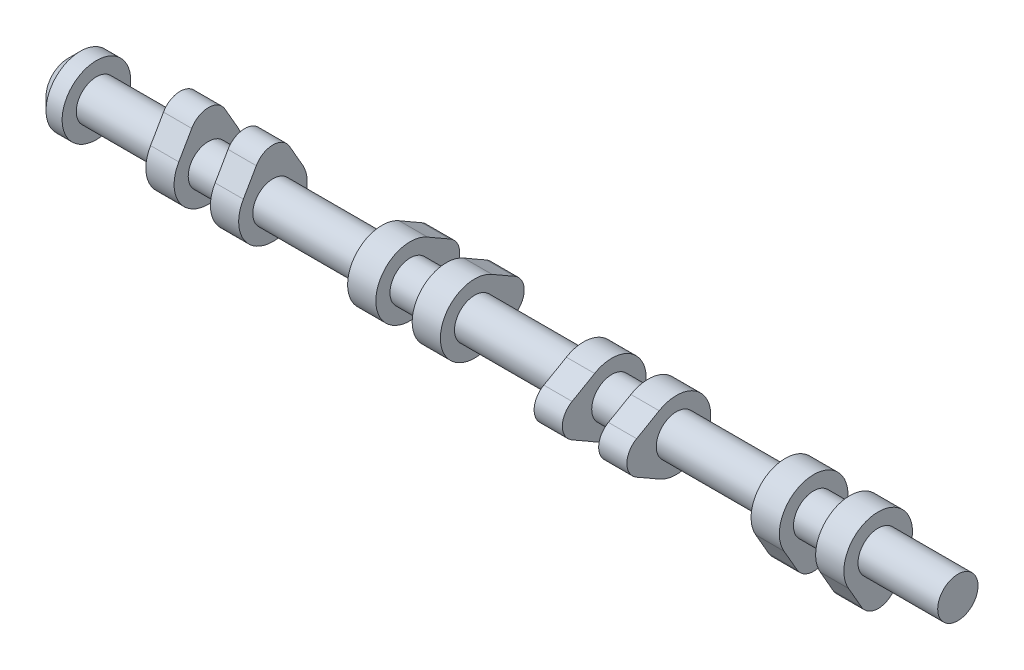
SolidWorks part; units mm, degrees
note: The reader was unsure of these and kept them because the rebuilt part matched: shared geometry of "Sketch1<5>", "Sketch1<6>".
ref_plane "Front Plane" through (0, 0, 0) normal (0, 0, 1) x (1, 0, 0)
ref_plane "Top Plane" through (0, 0, 0) normal (0, 1, 0) x (1, 0, 0)
ref_plane "Right Plane" through (0, 0, 0) normal (1, 0, 0) x (0, 0, -1)
sketch "Sketch1" plane through (0, 0, 0) normal (0, 0, 1) x (1, 0, 0)
  line L0 (0, 0) -> (10, 0)
  line L1 (10, 0) -> (46.5, 0)
  line L2 (46.5, 0) -> (78.5, 0)
  line L3 (78.5, 0) -> (146.5, 0)
  line L4 (146.5, 0) -> (178.5, 0)
  line L5 (178.5, 0) -> (246.5, 0)
  line L6 (246.5, 0) -> (278.5, 0)
  line L7 (278.5, 0) -> (346.5, 0)
  line L8 (346.5, 0) -> (378.5, 0)
  line L9 (378.5, 0) -> (415, 0)
  line L10 (415, 0) -> (425, 0)
  line L11 (39.5, 0) -> (53.5, 0) construction
  line L12 (71.5, 0) -> (85.5, 0) construction
  line L13 (139.5, 0) -> (153.5, 0) construction
  line L14 (185.5, 0) -> (171.5, 0) construction
  line L15 (239.5, 0) -> (253.5, 0)
  line L16 (271.5, 0) -> (285.5, 0)
  line L17 (339.5, 0) -> (353.5, 0)
  line L18 (371.5, 0) -> (385.5, 0)
  line L19 (139.5, 0) -> (139.5, 7)
  line L20 (0, 0) -> (425, 0)
  line L21 (0, 0) -> (0, -10)
  line L22 (0, -10) -> (425, -10)
  line L23 (425, 0) -> (425, -10)
  line L24 (39.5, 0) -> (53.5, 0)
  line L25 (39.5, 0) -> (39.5, 7)
  line L26 (39.5, 7) -> (53.5, 7)
  line L27 (53.5, 0) -> (53.5, 7)
  line L28 (85.5, 0) -> (71.5, 0)
  line L29 (85.5, 0) -> (85.5, 7)
  line L30 (85.5, 7) -> (71.5, 7)
  line L31 (71.5, 0) -> (71.5, 7)
  line L32 (139.5, 0) -> (153.5, 0)
  line L33 (153.5, 0) -> (153.5, 7)
  line L34 (139.5, 7) -> (153.5, 7)
  line L35 (185.5, 0) -> (185.5, 7)
  line L36 (185.5, 0) -> (171.5, 0)
  line L37 (171.5, 0) -> (171.5, 7)
  line L38 (185.5, 7) -> (171.5, 7)
  line L39 (239.5, 0) -> (239.5, 7)
  line L40 (239.5, 0) -> (253.5, 0)
  line L41 (253.5, 0) -> (253.5, 7)
  line L42 (239.5, 7) -> (253.5, 7)
  line L43 (285.5, 0) -> (285.5, 7)
  line L44 (285.5, 0) -> (271.5, 0)
  line L45 (271.5, 0) -> (271.5, 7)
  line L46 (285.5, 7) -> (271.5, 7)
  line L47 (339.5, 0) -> (339.5, 7)
  line L48 (339.5, 0) -> (353.5, 0)
  line L49 (353.5, 0) -> (353.5, 7)
  line L50 (339.5, 7) -> (353.5, 7)
  line L51 (385.5, 0) -> (385.5, 7)
  line L52 (385.5, 0) -> (371.5, 0)
  line L53 (371.5, 0) -> (371.5, 7)
  line L54 (385.5, 7) -> (371.5, 7)
  line L55 (53.5, 0) -> (54.5, 0)
  line L56 (54.5, 0) -> (70.5, 0)
  line L57 (70.5, 0) -> (71.5, 0)
  line L58 (154.5, 0) -> (154.5, 7)
  line L59 (54.5, 0) -> (70.5, 0)
  line L60 (54.5, 0) -> (54.5, 7)
  line L61 (54.5, 7) -> (70.5, 7)
  line L62 (70.5, 0) -> (70.5, 7)
  line L63 (154.5, 0) -> (170.5, 0)
  line L64 (170.5, 0) -> (170.5, 7)
  line L65 (154.5, 7) -> (170.5, 7)
  line L66 (254.5, 0) -> (254.5, 7)
  line L67 (254.5, 0) -> (270.5, 0)
  line L68 (270.5, 0) -> (270.5, 7)
  line L69 (254.5, 7) -> (270.5, 7)
  line L70 (354.5, 0) -> (354.5, 7)
  line L71 (354.5, 0) -> (370.5, 0)
  line L72 (370.5, 0) -> (370.5, 7)
  line L73 (354.5, 7) -> (370.5, 7)
  point P16 (46.5, 0)
  point P19 (78.5, 0)
  point P22 (146.5, 0)
  point P25 (178.5, 0)
  point P28 (246.5, 0)
  point P31 (278.5, 0)
  point P34 (346.5, 0)
  point P37 (378.5, 0)
  dimension "D1" = 10
  dimension "D2" = 36.5
  dimension "D3" = 32
  dimension "D4" = 68
  dimension "D5" = 32
  dimension "D6" = 68
  dimension "D7" = 32
  dimension "D8" = 68
  dimension "D9" = 32
  dimension "D10" = 36.5
  dimension "D11" = 10
  dimension "D12" = 14
  dimension "D13" = 14
  dimension "D14" = 14
  dimension "D15" = 14
  dimension "D16" = 14
  dimension "D17" = 14
  dimension "D18" = 14
  dimension "D19" = 14
  dimension "D20" = 10
  dimension "D21" = 7
  dimension "D23" = 1
  dimension "D24" = 1
  dimension "D25" = 16
  dimension "D22" = 4
  dimension "D26" = 4
revolve "Revolve1" add sketch "Sketch1" angle 360 about L22
revolve "Revolve2" add sketch "Sketch1<5>" angle 360 about L22
sketch "Sketch1<5>" plane through (0, 0, 0) normal (0, 0, 1) x (1, 0, 0) same geometry as "Sketch1"
sketch "Sketch2" plane through (39.5, 0, 0) normal (-1, 0, 0) x (0, 0, 1)
  line L0 (0, 0) -> (0, 7)
  line L1 (0, 7) -> (0, 15)
  line L2 (-6, 15) -> (6, 15)
  line L3 (-6, 15) -> (-17, -10)
  line L4 (-17, -10) -> (0, -10)
  line L5 (0, -10) -> (17, -10)
  line L6 (17, -10) -> (6, 15)
  circle A0 centre (0, -10) radius 17 construction
  point P11 (0, 15)
  circle M4 centre (0, -10) radius 17
  dimension "D1" = 8
  dimension "D2" = 7
  dimension "D3" = 12
extrude "Boss-Extrude2" add sketch "Sketch2" against normal blind 14 contours L6 L2 L1 M4 | L2 L3 L1 M4
fillet "Fillet3" radius 9.5 4 edges at (39.5, 15, 0) (46.5, 15, -6) (46.5, 15, 6) (53.5, 15, 0)
fillet "Fillet5" radius 1000 2 edges at (46.5, 2.5335, 11.4853) (46.5, 2.5335, -11.4853)
sketch "Lobe sketch" plane through (39.5, 0, 0) normal (-1, 0, 0) x (0, 0, 1)
  arc A15 (-14.6833, -1.4325) -> (14.6833, -1.4325) centre (0, -10) ccw
  arc A16 (8.2663, 9.7295) -> (14.6833, -1.4325) centre (878.4044, 502.5375) ccw
  arc A17 (8.2663, 9.7295) -> (-8.2663, 9.7295) centre (0, 5.0479) ccw
  arc A18 (-14.6833, -1.4325) -> (-8.2663, 9.7295) centre (-878.4044, 502.5375) ccw
  arc A19 (-14.6833, -1.4325) -> (14.6833, -1.4325) centre (0, -10) ccw
  arc A20 (8.2663, 9.7295) -> (14.6833, -1.4325) centre (878.4044, 502.5375) ccw
  arc A21 (8.2663, 9.7295) -> (-8.2663, 9.7295) centre (0, 5.0479) ccw
  arc A22 (-14.6833, -1.4325) -> (-8.2663, 9.7295) centre (-878.4044, 502.5375) ccw
  dimension "D1" = 0
sketch "Sketch10" plane through (71.5, 0, 0) normal (-1, 0, 0) x (0, 0, 1)
  circle A1 centre (0, -10) radius 17
  circle A2 centre (0, -10) radius 17
  arc A6 (-14.6833, -1.4325) -> (14.6833, -1.4325) centre (0, -10) ccw
  arc A7 (8.2663, 9.7295) -> (14.6833, -1.4325) centre (878.4044, 502.5375) ccw
  arc A8 (8.2663, 9.7295) -> (-8.2663, 9.7295) centre (0, 5.0479) ccw
  arc A9 (-14.6833, -1.4325) -> (-8.2663, 9.7295) centre (-878.4044, 502.5375) ccw
  arc A10 (-14.6833, -1.4325) -> (14.6833, -1.4325) centre (0, -10) ccw
  arc A11 (8.2663, 9.7295) -> (14.6833, -1.4325) centre (878.4044, 502.5375) ccw
  arc A12 (8.2663, 9.7295) -> (-8.2663, 9.7295) centre (0, 5.0479) ccw
  arc A13 (-14.6833, -1.4325) -> (-8.2663, 9.7295) centre (-878.4044, 502.5375) ccw
  circle M6 centre (0, -10) radius 17
  dimension "D1" = 0
  dimension "D2" = 0
extrude "Boss-Extrude5" add sketch "Sketch10" against normal blind 14 contours A13 A11 A12 M6
sketch "Sketch11" plane through (239.5, 0, 0) normal (-1, 0, 0) x (0, 0, 1)
  circle A3 centre (0, -10) radius 17
  arc A11 (19.7295, -18.2663) -> (19.7295, -1.7337) centre (15.0479, -10) ccw
  arc A12 (19.7295, -18.2663) -> (8.5675, -24.6833) centre (512.5375, -888.4044) ccw
  arc A13 (8.5675, 4.6833) -> (8.5675, -24.6833) centre (0, -10) ccw
  arc A14 (8.5675, 4.6833) -> (19.7295, -1.7337) centre (512.5375, 868.4044) ccw
  circle M6 centre (0, -10) radius 17
extrude "Boss-Extrude6" add sketch "Sketch11" against normal blind 14 contours A14 A12 A11 M6
sketch "Sketch12" plane through (271.5, 0, 0) normal (-1, 0, 0) x (0, 0, 1)
  circle A1 centre (0, -10) radius 17
  circle A2 centre (0, -10) radius 17
  arc A10 (19.7295, -18.2663) -> (19.7295, -1.7337) centre (15.0479, -10) ccw
  arc A11 (19.7295, -18.2663) -> (8.5675, -24.6833) centre (512.5375, -888.4044) ccw
  arc A12 (8.5675, 4.6833) -> (8.5675, -24.6833) centre (0, -10) ccw
  arc A13 (8.5675, 4.6833) -> (19.7295, -1.7337) centre (512.5375, 868.4044) ccw
  dimension "D1" = 0
extrude "Boss-Extrude7" add sketch "Sketch12" against normal blind 14 contours A10 A13 A12 A11
sketch "Sketch13" plane through (339.5, 0, 0) normal (-1, 0, 0) x (0, 0, 1)
  circle A1 centre (0, -10) radius 17
  circle A2 centre (0, -10) radius 17
  arc A10 (-8.2663, -29.7295) -> (8.2663, -29.7295) centre (0, -25.0479) ccw
  arc A11 (-8.2663, -29.7295) -> (-14.6833, -18.5675) centre (-878.4044, -522.5375) ccw
  arc A12 (14.6833, -18.5675) -> (-14.6833, -18.5675) centre (0, -10) ccw
  arc A13 (14.6833, -18.5675) -> (8.2663, -29.7295) centre (878.4044, -522.5375) ccw
  dimension "D1" = 0
sketch "Sketch14" plane through (371.5, 0, 0) normal (-1, 0, 0) x (0, 0, 1)
  circle A1 centre (0, -10) radius 17
  circle A2 centre (0, -10) radius 17
  arc A10 (-8.2663, -29.7295) -> (8.2663, -29.7295) centre (0, -25.0479) ccw
  arc A11 (-8.2663, -29.7295) -> (-14.6833, -18.5675) centre (-878.4044, -522.5375) ccw
  arc A12 (14.6833, -18.5675) -> (-14.6833, -18.5675) centre (0, -10) ccw
  arc A13 (14.6833, -18.5675) -> (8.2663, -29.7295) centre (878.4044, -522.5375) ccw
  dimension "D1" = 0
extrude "Boss-Extrude8" add sketch "Sketch14" against normal blind 14 contours A10 A13 A12 A11
extrude "Boss-Extrude9" add sketch "Sketch13" against normal blind 14 contours A10 A13 A12 A11
sketch "Sketch15" plane through (139.5, 0, 0) normal (-1, 0, 0) x (0, 0, 1)
  arc A8 (-19.7295, -1.7337) -> (-19.7295, -18.2663) centre (-15.0479, -10) ccw
  arc A9 (-19.7295, -1.7337) -> (-8.5675, 4.6833) centre (-512.5375, 868.4044) ccw
  arc A10 (-8.5675, -24.6833) -> (-8.5675, 4.6833) centre (0, -10) ccw
  arc A11 (-8.5675, -24.6833) -> (-19.7295, -18.2663) centre (-512.5375, -888.4044) ccw
sketch "Sketch16" plane through (171.5, 0, 0) normal (-1, 0, 0) x (0, 0, 1)
  arc A8 (-19.7295, -1.7337) -> (-19.7295, -18.2663) centre (-15.0479, -10) ccw
  arc A9 (-19.7295, -1.7337) -> (-8.5675, 4.6833) centre (-512.5375, 868.4044) ccw
  arc A10 (-8.5675, -24.6833) -> (-8.5675, 4.6833) centre (0, -10) ccw
  arc A11 (-8.5675, -24.6833) -> (-19.7295, -18.2663) centre (-512.5375, -888.4044) ccw
extrude "Boss-Extrude10" add sketch "Sketch15" against normal blind 14 contours A8 A11 A10 A9
extrude "Boss-Extrude11" add sketch "Sketch16" against normal blind 14 contours A8 A11 A10 A9
revolve "Revolve3" add sketch "Sketch1<6>" angle 360 about L22
sketch "Sketch1<6>" plane through (0, 0, 0) normal (0, 0, 1) x (1, 0, 0) same geometry as "Sketch1"
sketch "Sketch17" plane through (54.5, 0, 0) normal (-1, 0, 0) x (0, 0, 1)
  line L0 (0, 7) -> (0, 10)
  line L1 (0, 0) -> (0, 7) construction
  line L2 (2, -30) -> (-2, -30)
  line L3 (0, 10) -> (0, -10) construction
  line L4 (17, -10) -> (-17, -10)
  line L5 (17, -10) -> (2, -30)
  line L6 (-2, -30) -> (-17, -10)
  point P8 (0, -30)
  point P15 (0, -10)
  dimension "D1" = 3
  dimension "D2" = 4
extrude "Boss-Extrude12" add sketch "Sketch17" against normal blind 16 contours L2 L6 L4 L5
fillet "Fillet6" radius 1000 2 edges at (62.5, -26.32, -4.76) (62.5, -26.32, 4.76)
fillet "Fillet7" radius 4 2 edges at (62.5, -30, -2) (62.5, -30, 2)
sketch "PD Lobe sketch" plane through (54.5, 0, 0) normal (-1, 0, 0) x (0, 0, 1)
  line L2 (-0.6141, -30) -> (0.6141, -30)
  line L3 (-0.6141, -30) -> (0.6141, -30)
  arc A10 (-3.0867, -29.1442) -> (-10.3846, -23.4596) centre (-621.2411, -815.2009) ccw
  arc A11 (-3.0867, -29.1442) -> (-0.6141, -30) centre (-0.6141, -26) ccw
  arc A12 (0.6141, -30) -> (3.0867, -29.1442) centre (0.6141, -26) ccw
  arc A13 (10.3846, -23.4596) -> (3.0867, -29.1442) centre (621.2411, -815.2009) ccw
  arc A14 (10.3846, -23.4596) -> (-10.3846, -23.4596) centre (0, -10) ccw
  arc A15 (-3.0867, -29.1442) -> (-10.3846, -23.4596) centre (-621.2411, -815.2009) ccw
  arc A16 (-3.0867, -29.1442) -> (-0.6141, -30) centre (-0.6141, -26) ccw
  arc A17 (0.6141, -30) -> (3.0867, -29.1442) centre (0.6141, -26) ccw
  arc A18 (10.3846, -23.4596) -> (3.0867, -29.1442) centre (621.2411, -815.2009) ccw
  arc A19 (10.3846, -23.4596) -> (-10.3846, -23.4596) centre (0, -10) ccw
  dimension "D1" = 0
sketch "Sketch19" plane through (154.5, 0, 0) normal (-1, 0, 0) x (0, 0, 1)
  line L3 (20, -10.6141) -> (20, -9.3859)
  arc A15 (20, -9.3859) -> (19.1442, -6.9133) centre (16, -9.3859) ccw
  arc A16 (13.4596, 0.3846) -> (19.1442, -6.9133) centre (805.2009, 611.2411) ccw
  arc A17 (13.4596, 0.3846) -> (13.4596, -20.3846) centre (0, -10) ccw
  arc A18 (19.1442, -13.0867) -> (13.4596, -20.3846) centre (805.2009, -631.2411) ccw
  arc A19 (19.1442, -13.0867) -> (20, -10.6141) centre (16, -10.6141) ccw
sketch "Sketch20" plane through (254.5, 0, 0) normal (-1, 0, 0) x (0, 0, 1)
  line L2 (-20, -9.3859) -> (-20, -10.6141)
  arc A10 (-20, -10.6141) -> (-19.1442, -13.0867) centre (-16, -10.6141) ccw
  arc A11 (-13.4596, -20.3846) -> (-19.1442, -13.0867) centre (-805.2009, -631.2411) ccw
  arc A12 (-13.4596, -20.3846) -> (-13.4596, 0.3846) centre (0, -10) ccw
  arc A13 (-19.1442, -6.9133) -> (-13.4596, 0.3846) centre (-805.2009, 611.2411) ccw
  arc A14 (-19.1442, -6.9133) -> (-20, -9.3859) centre (-16, -9.3859) ccw
sketch "Sketch21" plane through (354.5, 0, 0) normal (-1, 0, 0) x (0, 0, 1)
  line L2 (0.6141, 10) -> (-0.6141, 10)
  arc A10 (-0.6141, 10) -> (-3.0867, 9.1442) centre (-0.6141, 6) ccw
  arc A11 (-10.3846, 3.4596) -> (-3.0867, 9.1442) centre (-621.2411, 795.2009) ccw
  arc A12 (-10.3846, 3.4596) -> (10.3846, 3.4596) centre (0, -10) ccw
  arc A13 (3.0867, 9.1442) -> (10.3846, 3.4596) centre (621.2411, 795.2009) ccw
  arc A14 (3.0867, 9.1442) -> (0.6141, 10) centre (0.6141, 6) ccw
extrude "Boss-Extrude13" add sketch "Sketch21" against normal blind 16
extrude "Boss-Extrude14" add sketch "Sketch20" against normal blind 16
extrude "Boss-Extrude15" add sketch "Sketch19" against normal blind 16
sketch "Sketch22" plane through (0, 0, 0) normal (-1, 0, 0) x (0, 0, 1)
  circle A0 centre (0, -10) radius 17
extrude "Front" add sketch "Sketch22" along normal blind 16 contours A0
chamfer "Chamfer1" distance 6 angle 45 1 edges at (-16, -10, 17)
sketch "Sketch23" plane through (-16, 0, 0) normal (-1, 0, 0) x (0, 0, 1)
  circle A0 centre (0, -10) radius 6
  dimension "D1" = 12
extrude "Cut-Extrude1" cut sketch "Sketch23" against normal blind 40 contours A0
sketch "Sketch24" plane through (0, 0, 0) normal (1, 0, 0) x (0, 0, -1)
  circle A0 centre (0, -10) radius 10
  circle A1 centre (0, -10) radius 17
extrude "Cut-Extrude2" cut sketch "Sketch24" against normal blind 2
sketch "Sketch25" plane through (54.5, 0, 0) normal (-1, 0, 0) x (0, 0, 1)
  line L2 (-0.6141, -30) -> (0.6141, -30)
  line L3 (-0.6141, -30) -> (0.6141, -30)
  arc A10 (-3.0867, -29.1442) -> (-10.3846, -23.4596) centre (-621.2411, -815.2009) ccw
  arc A11 (-3.0867, -29.1442) -> (-0.6141, -30) centre (-0.6141, -26) ccw
  arc A12 (0.6141, -30) -> (3.0867, -29.1442) centre (0.6141, -26) ccw
  arc A13 (10.3846, -23.4596) -> (3.0867, -29.1442) centre (621.2411, -815.2009) ccw
  arc A14 (10.3846, -23.4596) -> (-10.3846, -23.4596) centre (0, -10) ccw
  arc A15 (-3.0867, -29.1442) -> (-10.3846, -23.4596) centre (-621.2411, -815.2009) ccw
  arc A16 (-3.0867, -29.1442) -> (-0.6141, -30) centre (-0.6141, -26) ccw
  arc A17 (0.6141, -30) -> (3.0867, -29.1442) centre (0.6141, -26) ccw
  arc A18 (10.3846, -23.4596) -> (3.0867, -29.1442) centre (621.2411, -815.2009) ccw
  arc A19 (10.3846, -23.4596) -> (-10.3846, -23.4596) centre (0, -10) ccw
  dimension "D1" = 0
sketch "Sketch26" plane through (154.5, 0, 0) normal (-1, 0, 0) x (0, 0, 1)
  line L2 (20, -10.6141) -> (20, -9.3859)
  line L3 (20, -10.6141) -> (20, -9.3859)
  arc A10 (13.4596, 0.3846) -> (13.4596, -20.3846) centre (0, -10) ccw
  arc A11 (19.1442, -13.0867) -> (13.4596, -20.3846) centre (805.2009, -631.2411) ccw
  arc A12 (19.1442, -13.0867) -> (20, -10.6141) centre (16, -10.6141) ccw
  arc A13 (20, -9.3859) -> (19.1442, -6.9133) centre (16, -9.3859) ccw
  arc A14 (13.4596, 0.3846) -> (19.1442, -6.9133) centre (805.2009, 611.2411) ccw
  arc A15 (13.4596, 0.3846) -> (13.4596, -20.3846) centre (0, -10) ccw
  arc A16 (19.1442, -13.0867) -> (13.4596, -20.3846) centre (805.2009, -631.2411) ccw
  arc A17 (19.1442, -13.0867) -> (20, -10.6141) centre (16, -10.6141) ccw
  arc A18 (20, -9.3859) -> (19.1442, -6.9133) centre (16, -9.3859) ccw
  arc A19 (13.4596, 0.3846) -> (19.1442, -6.9133) centre (805.2009, 611.2411) ccw
  dimension "D1" = 0
sketch "Sketch27" plane through (254.5, 0, 0) normal (-1, 0, 0) x (0, 0, 1)
  line L2 (-20, -9.3859) -> (-20, -10.6141)
  line L3 (-20, -9.3859) -> (-20, -10.6141)
  arc A10 (-13.4596, -20.3846) -> (-13.4596, 0.3846) centre (0, -10) ccw
  arc A11 (-19.1442, -6.9133) -> (-13.4596, 0.3846) centre (-805.2009, 611.2411) ccw
  arc A12 (-19.1442, -6.9133) -> (-20, -9.3859) centre (-16, -9.3859) ccw
  arc A13 (-20, -10.6141) -> (-19.1442, -13.0867) centre (-16, -10.6141) ccw
  arc A14 (-13.4596, -20.3846) -> (-19.1442, -13.0867) centre (-805.2009, -631.2411) ccw
  arc A15 (-13.4596, -20.3846) -> (-13.4596, 0.3846) centre (0, -10) ccw
  arc A16 (-19.1442, -6.9133) -> (-13.4596, 0.3846) centre (-805.2009, 611.2411) ccw
  arc A17 (-19.1442, -6.9133) -> (-20, -9.3859) centre (-16, -9.3859) ccw
  arc A18 (-20, -10.6141) -> (-19.1442, -13.0867) centre (-16, -10.6141) ccw
  arc A19 (-13.4596, -20.3846) -> (-19.1442, -13.0867) centre (-805.2009, -631.2411) ccw
  dimension "D1" = 0
sketch "Sketch28" plane through (354.5, 0, 0) normal (-1, 0, 0) x (0, 0, 1)
  line L2 (0.6141, 10) -> (-0.6141, 10)
  line L3 (0.6141, 10) -> (-0.6141, 10)
  arc A10 (-10.3846, 3.4596) -> (10.3846, 3.4596) centre (0, -10) ccw
  arc A11 (3.0867, 9.1442) -> (10.3846, 3.4596) centre (621.2411, 795.2009) ccw
  arc A12 (3.0867, 9.1442) -> (0.6141, 10) centre (0.6141, 6) ccw
  arc A13 (-0.6141, 10) -> (-3.0867, 9.1442) centre (-0.6141, 6) ccw
  arc A14 (-10.3846, 3.4596) -> (-3.0867, 9.1442) centre (-621.2411, 795.2009) ccw
  arc A15 (-10.3846, 3.4596) -> (10.3846, 3.4596) centre (0, -10) ccw
  arc A16 (3.0867, 9.1442) -> (10.3846, 3.4596) centre (621.2411, 795.2009) ccw
  arc A17 (3.0867, 9.1442) -> (0.6141, 10) centre (0.6141, 6) ccw
  arc A18 (-0.6141, 10) -> (-3.0867, 9.1442) centre (-0.6141, 6) ccw
  arc A19 (-10.3846, 3.4596) -> (-3.0867, 9.1442) centre (-621.2411, 795.2009) ccw
  dimension "D1" = 0
extrude "Cut-Extrude4" cut sketch "Sketch28" against normal blind 16
extrude "Cut-Extrude5" cut sketch "Sketch27" against normal blind 16
extrude "Cut-Extrude6" cut sketch "Sketch26" against normal blind 16
extrude "Cut-Extrude7" cut sketch "Sketch25" against normal blind 16
sketch "Sketch30" plane through (54.5, 0, 0) normal (1, 0, 0) x (0, 0, -1)
  circle A0 centre (0, -10) radius 10
sketch "Sketch31" plane through (154.5, 0, 0) normal (1, 0, 0) x (0, 0, -1)
  circle A0 centre (0, -10) radius 10
sketch "Sketch32" plane through (254.5, 0, 0) normal (1, 0, 0) x (0, 0, -1)
  circle A0 centre (0, -10) radius 10
sketch "Sketch33" plane through (354.5, 0, 0) normal (1, 0, 0) x (0, 0, -1)
  circle A0 centre (0, -10) radius 10
extrude "Boss-Extrude16" add sketch "Sketch33" along normal blind 16
extrude "Boss-Extrude17" add sketch "Sketch32" along normal blind 16
extrude "Boss-Extrude18" add sketch "Sketch31" along normal blind 16
extrude "Boss-Extrude19" add sketch "Sketch30" along normal blind 16
